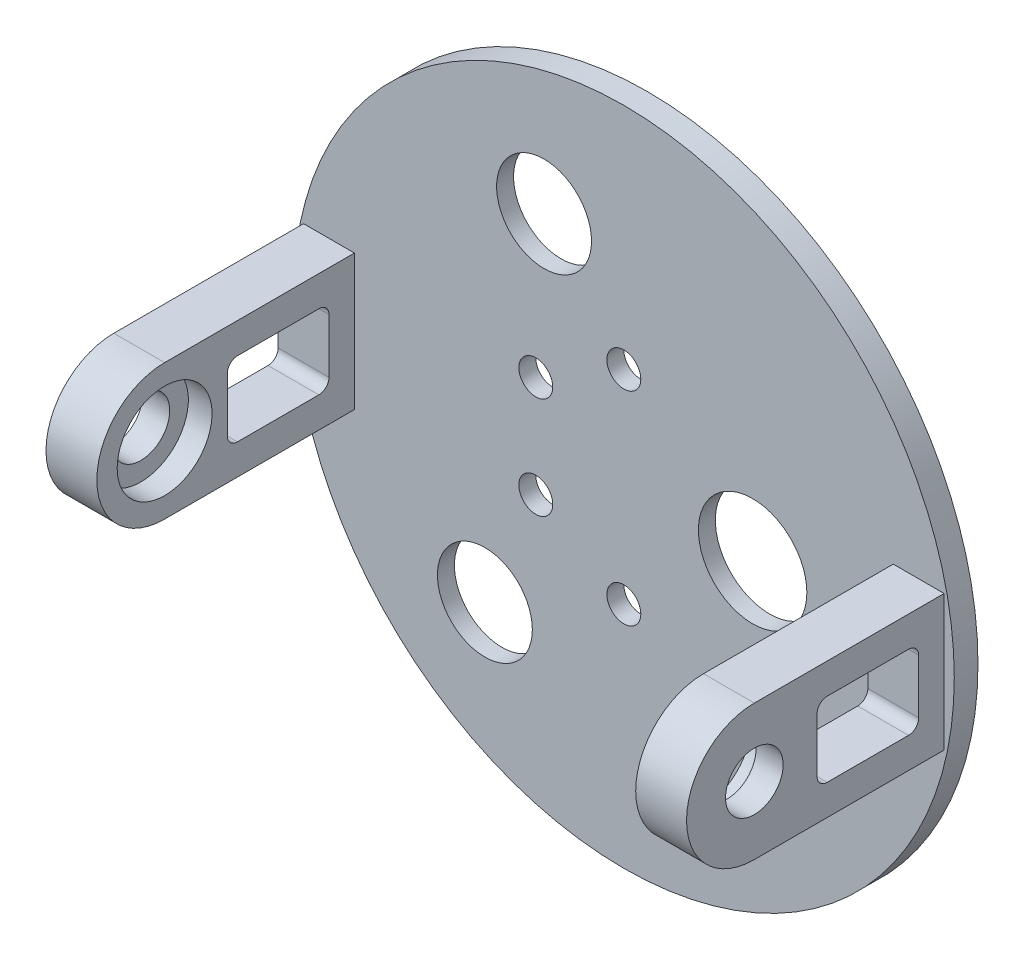
SolidWorks part; units mm, degrees
ref_plane "Front Plane" through (0, 0, 0) normal (0, 0, 1) x (1, 0, 0)
ref_plane "Top Plane" through (0, 0, 0) normal (0, 1, 0) x (1, 0, 0)
ref_plane "Right Plane" through (0, 0, 0) normal (1, 0, 0) x (0, 0, -1)
sketch "Sketch1" plane through (0, 0, 0) normal (0, 0, 1) x (1, 0, 0)
  circle A0 centre (0, 0) radius 97.5
  circle A1 centre (38, 0) radius 16
  dimension "D1" = 195
  dimension "D2" = 32
  dimension "D3" = 38
extrude "Boss-Extrude1" add sketch "Sketch1" along normal mid plane 5
sketch "Sketch2" plane through (0, 0, 2.5) normal (0, 0, 1) x (1, 0, 0)
  circle A0 centre (0, 30) radius 5
  dimension "D1" = 10
  dimension "D2" = 30
extrude "Cut-Extrude1" cut sketch "Sketch2" against normal through all
ref_axis "Axis1" through (0, 0, 2.5) along (0, 0, -1)
pattern_circular "CirPattern1" count 4 every 60 about axis through (0, 0, 2.5) along (0, 0, -1) of "Cut-Extrude1" reverse direction yes
sketch "Sketch4" plane through (0, 0, -2.5) normal (0, 0, -1) x (-1, 0, 0)
  circle A0 centre (0, 0) radius 97.5 construction
  circle A1 centre (0, 0) radius 97.5
  circle A2 centre (0, 0) radius 94.5
  dimension "D1" = 3
extrude "Boss-Extrude2" add sketch "Sketch4" along normal blind 2
ref_plane "Plane1" through (87, 0, 0) normal (1, 0, 0) x (0, 0, -1)
sketch "Sketch5" plane through (87, 0, 0) normal (1, 0, 0) x (0, 0, -1)
  line L0 (-2.5, 97.5) -> (-2.5, -97.5) construction
  line L1 (-58.5, 20) -> (-2.5, 20)
  line L2 (-58.5, 20) -> (-58.5, -20)
  line L3 (-58.5, -20) -> (-2.5, -20)
  line L4 (-2.5, 20) -> (-2.5, -20)
  line L5 (-58.5, 20) -> (-2.5, -20) construction
  line L6 (-58.5, -20) -> (-2.5, 20) construction
  circle A0 centre (-58.5, 0) radius 20
  circle A1 centre (-58.5, 0) radius 8.5
  point P0 (-30.5, 0)
  dimension "D1" = 40
  dimension "D2" = 17
  dimension "D3" = 58.5
extrude "Boss-Extrude3" add sketch "Sketch5" against normal mid plane 15 contours A0 L3 L4 L1 | A1 L2 A0 | A1 L2 A0 region at (87, 0, 48.9358) region at (87, 0, 22.8933) region at (87, 0, 68.0642)
sketch "Sketch6" plane through (79.5, 0, 0) normal (-1, 0, 0) x (0, 0, 1)
  circle A0 centre (58.5, 0) radius 14
  dimension "D1" = 28
extrude "Cut-Extrude2" cut sketch "Sketch6" against normal blind 7
sketch "Sketch7" plane through (94.5, 0, 0) normal (1, 0, 0) x (0, 0, -1)
  line L1 (-13, 11) -> (-37, 11)
  line L2 (-10, 8) -> (-10, -8)
  line L3 (-13, -11) -> (-37, -11)
  line L4 (-40, 8) -> (-40, -8)
  line L5 (-10, 11) -> (-40, -11) construction
  line L6 (-10, -11) -> (-40, 11) construction
  arc A0 (-37, -11) -> (-40, -8) centre (-37, -8) cw
  arc A1 (-10, -8) -> (-13, -11) centre (-13, -8) cw
  arc A2 (-13, 11) -> (-10, 8) centre (-13, 8) cw
  arc A3 (-37, 11) -> (-40, 8) centre (-37, 8) ccw
  point P0 (-25, 0)
  dimension "D4" = 3
  dimension "D1" = 25
  dimension "D2" = 22
  dimension "D3" = 30
extrude "Cut-Extrude3" cut sketch "Sketch7" against normal up to next
mirror "Mirror1" about plane through (0, 0, 0) normal (1, 0, 0) of "Cut-Extrude3", "Cut-Extrude2", "Boss-Extrude3"
sketch "Sketch8" plane through (0, 0, 2.5) normal (0, 0, 1) x (1, 0, 0)
  circle A0 centre (-41, -50) radius 14
  dimension "D1" = 28
  dimension "D2" = 41
  dimension "D3" = 50
extrude "Cut-Extrude4" cut sketch "Sketch8" against normal up to next
sketch "Sketch9" plane through (0, 0, 2.5) normal (0, 0, 1) x (1, 0, 0)
  line L0 (-41, -50) -> (-44.4452, 102.1622) construction
  circle A0 centre (-23.5402, 58) radius 14
  dimension "D1" = 19.9
  dimension "D3" = 28
  dimension "D2" = 108
extrude "Cut-Extrude5" cut sketch "Sketch9" against normal through all
